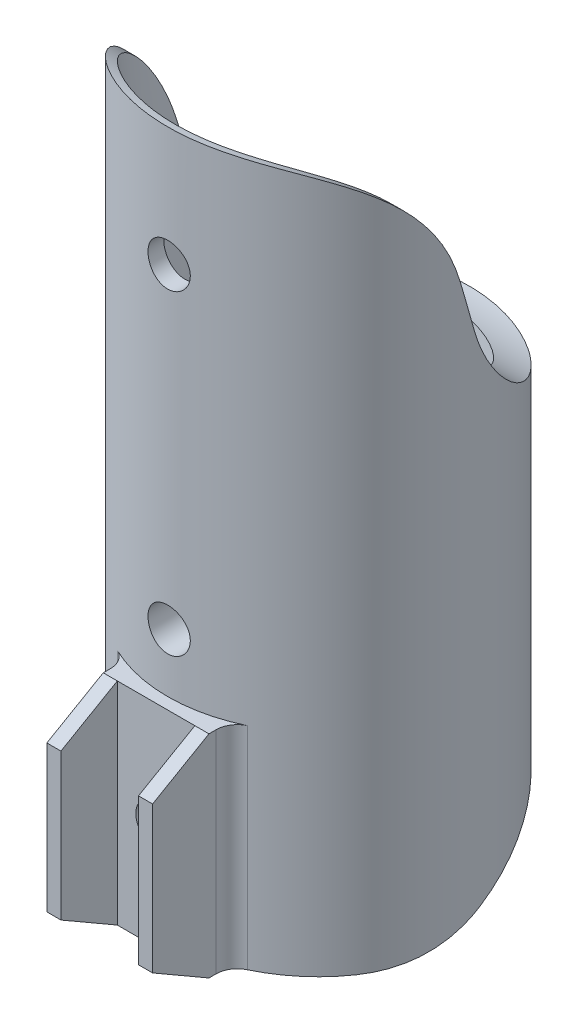
SolidWorks part; units mm, degrees
ref_plane "Front Plane" through (0, 0, 0) normal (0, 0, 1) x (1, 0, 0)
ref_plane "Top Plane" through (0, 0, 0) normal (0, 1, 0) x (1, 0, 0)
ref_plane "Right Plane" through (0, 0, 0) normal (1, 0, 0) x (0, 0, -1)
sketch "Sketch2" plane through (0, 0, 0) normal (0, 1, 0) x (1, 0, 0)
  circle A0 centre (0, 0) radius 21.36
  circle A1 centre (0, 0) radius 12.7
  circle A2 centre (0, 0) radius 17.36
  dimension "D1" = 42.72
  dimension "D2" = 25.4
  dimension "D3" = 4
extrude "Boss-Extrude1" add sketch "Sketch2" along normal blind 70 contours A0 A2 region at (-20.7558, 0, 0)
sketch "Sketch3" plane through (0, 0, 0) normal (1, 0, 0) x (0, 0, -1)
  line L1 (-21.36, 70) -> (21.36, 70)
  line L4 (21.36, 70) -> (21.36, 29.1276)
  line L5 (0.7565, 44.6971) -> (-1.2124, 51.634)
  line L6 (21.36, 0) -> (21.36, 70) construction
  arc A0 (-1.2124, 51.634) -> (-21.36, 70) centre (-26.0952, 44.5715) ccw
  arc A1 (0.7565, 44.6971) -> (21.36, 29.1276) centre (21.36, 50.545) ccw
extrude "Cut-Extrude1" cut sketch "Sketch3" against normal through all both and the other way through all
sketch "Sketch4" plane through (0, 0, 0) normal (0, -1, 0) x (1, 0, 0)
  line L0 (-4.9725, -16.6326) -> (-5.6964, -18.503)
  line L1 (-4.6103, -15.697) -> (-5.6964, -18.503) construction
  line L2 (4.9725, -16.6326) -> (5.6964, -18.503)
  line L3 (5.6964, -18.503) -> (4.6103, -15.697) construction
  line L4 (-16.8905, 4.01) -> (-18.8723, 4.3183)
  line L5 (-11.9181, 12.6226) -> (-13.1759, 14.1847)
  line L6 (11.9181, 12.6226) -> (13.1759, 14.1847)
  line L7 (16.8905, 4.01) -> (18.8723, 4.3183)
  circle A0 centre (0, 0) radius 21.36
  arc A1 (4.9725, -16.6326) -> (16.8905, 4.01) centre (0, 0) ccw
  arc A2 (-5.6964, -18.503) -> (5.6964, -18.503) centre (0, 0) ccw
  arc A3 (18.8723, 4.3183) -> (13.1759, 14.1847) centre (0, 0) ccw
  arc A4 (-16.8905, 4.01) -> (-4.9725, -16.6326) centre (0, 0) ccw
  arc A5 (-13.1759, 14.1847) -> (-18.8723, 4.3183) centre (0, 0) ccw
  arc A6 (11.9181, 12.6226) -> (-11.9181, 12.6226) centre (0, 0) ccw
  point P23 (0, 0)
  dimension "D1" = 3
extrude "Boss-Extrude2" add sketch "Sketch4" along normal blind 30
sketch "Sketch5" plane through (0, -104.4031, 0) normal (1, 0, 0) x (0, 0, -1)
  line L0 (16.1152, 85.3374) -> (1.7048, 77.8113)
  line L1 (21.36, 85.3374) -> (21.36, 74.4031)
  line L2 (21.36, 74.4031) -> (-12.1832, 74.4031)
  line L7 (21.36, 85.3374) -> (21.36, 92.8008)
  line L8 (21.36, 92.8008) -> (16.1152, 92.8008)
  line L9 (16.1152, 85.3374) -> (16.1152, 92.8008)
  arc A0 (-12.1832, 74.4031) -> (1.7048, 77.8113) centre (-12.1832, 104.4031) ccw
  dimension "D1" = 30
extrude "Cut-Extrude2" cut sketch "Sketch5" against normal through all both and the other way through all
sketch "Sketch6" plane through (0, 0, 25.5) normal (0, 0, 1) x (1, 0, 0)
  line L0 (-17.5448, -30) -> (17.5448, -30) construction
  line L1 (-7.5, 0) -> (7.5, 0)
  line L2 (-7.5, 0) -> (-7.5, -30)
  line L3 (-7.5, -30) -> (7.5, -30)
  line L4 (7.5, 0) -> (7.5, -30)
  dimension "D1" = 15
extrude "Boss-Extrude5" add sketch "Sketch6" against normal blind 5 from offset 2.5 offset against normal yes
sketch "Sketch7" plane through (0, 0, 23) normal (0, 0, 1) x (1, 0, 0)
  circle A0 centre (0, -14.9681) radius 2.88
extrude "Cut-Extrude3" cut sketch "Sketch7" against normal up to next
sketch "Sketch8" plane through (0, 0, 23) normal (0, 0, 1) x (1, 0, 0)
  line L0 (-7.5, -30) -> (7.5, -30) construction
  line L1 (-7.5, 0) -> (-5.5, 0)
  line L2 (-7.5, 0) -> (-7.5, -30)
  line L3 (-7.5, -30) -> (-5.5, -30)
  line L4 (-5.5, 0) -> (-5.5, -30)
  line L5 (0, -129.5711) -> (0, -79.2351) construction
  line L6 (7.5, -30) -> (5.5, -30)
  line L7 (5.5, 0) -> (5.5, -30)
  line L8 (7.5, 0) -> (5.5, 0)
  line L9 (7.5, 0) -> (7.5, -30)
  dimension "D1" = 2
extrude "Boss-Extrude6" add sketch "Sketch8" along normal blind 8
chamfer "Chamfer1" distance 8 angle 30 4 edges at (6.5, -30, 31) (-6.5, -30, 31) (-6.5, 0, 31) (6.5, 0, 31) first distance on face at (0, -30, 19.9176) first distance on face at (0, 0, 26.42)
fillet "Fillet1" radius 3 2 edges at (-7.5, -15, 20) (7.5, -15, 20)
ref_plane "Plane1" through (0, 0, 21.36) normal (0, 0, 1) x (1, 0, 0)
sketch "Sketch13" plane through (0, -11.6023, 0) normal (0, -1, 0) x (1, 0, 0)
  line L0 (5.6964, -18.503) -> (4.6103, -15.697)
  line L2 (-5.6964, -18.503) -> (-4.6103, -15.697)
  line L4 (-18.8723, 4.3183) -> (-15.8991, 3.8559)
  line L5 (-13.1759, 14.1847) -> (-11.2888, 11.8411)
  line L6 (13.1759, 14.1847) -> (11.2888, 11.8411)
  line L7 (18.8723, 4.3183) -> (15.8991, 3.8559)
  circle A0 centre (0, 0) radius 21.36
  arc A1 (11.2888, 11.8411) -> (-11.2888, 11.8411) centre (0, 0) ccw
  arc A2 (-7.4939, 14.5427) -> (7.4939, 14.5427) centre (0, 0) ccw construction
  arc A4 (18.8723, 4.3183) -> (13.1759, 14.1847) centre (0, 0) ccw
  arc A5 (-5.6964, -18.503) -> (5.6964, -18.503) centre (0, 0) ccw
  arc A6 (-13.1759, 14.1847) -> (-18.8723, 4.3183) centre (0, 0) ccw
  arc A7 (-15.8991, 3.8559) -> (-4.6103, -15.697) centre (0, 0) ccw
  arc A8 (4.6103, -15.697) -> (15.8991, 3.8559) centre (0, 0) ccw
  point P25 (0, 0)
  dimension "D1" = 3
extrude "Boss-Extrude7" add sketch "Sketch13" against normal blind 40
sketch "Sketch12" plane through (0, -11.6023, 0) normal (0, -1, 0) x (1, 0, 0)
  circle A1 centre (0, 0) radius 16.36
  circle A4 centre (0, 0) radius 16.36 construction
extrude "Cut-Extrude4" cut sketch "Sketch12" against normal blind 65 draft 4 from offset 25 draft outward yes offset against normal yes
hole_wizard "Ø6.0 (6) Diameter Hole1" positions "Sketch9" profile "Sketch11" hole size "Ø6.0" standard "ANSI Metric"
sketch "Sketch9" plane through (0, 0, 21.36) normal (0, 0, 1) x (1, 0, 0)
  point P0 (0, 53.0753)
  point P5 (0, 8.258)
  point P6 (0, 8.258)
sketch "Sketch11" plane through (0, 53.0753, 21.36) normal (1, 0, 0) x (0, -1, 0)
  line L0 (0, 0) -> (0, 11.8026)
  line L1 (0, 11.8026) -> (3, 10)
  line L2 (3, 10) -> (3, 0)
  line L5 (3, 0) -> (0, 0)
  line L10 (0, 11.8026) -> (-3, 10) construction
  line L11 (0, -6.35) -> (0, 107.95) construction
  dimension "Hole Dia." = 6
  dimension "Hole Depth" = 10
  dimension "Drill Angle" = 118
